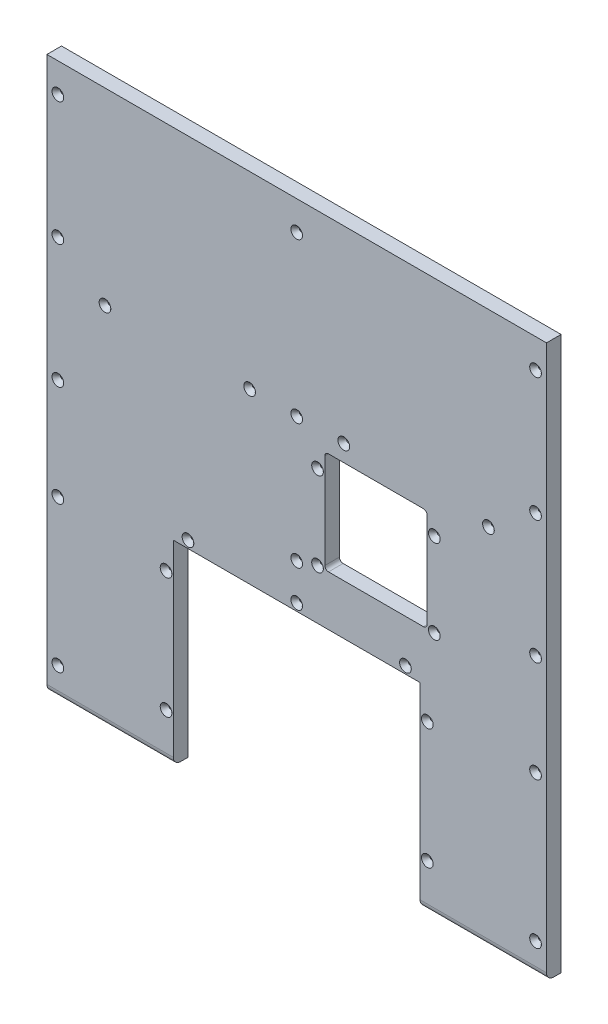
SolidWorks part; units mm, degrees
material "Beech"
ref_plane "Front Plane" through (0, 0, 0) normal (0, 0, 1) x (1, 0, 0)
ref_plane "Top Plane" through (0, 0, 0) normal (0, 1, 0) x (1, 0, 0)
ref_plane "Right Plane" through (0, 0, 0) normal (1, 0, 0) x (0, 0, -1)
sketch "Sketch1" plane through (0, 0, 0) normal (0, 0, 1) x (1, 0, 0)
  line L0 (124.0045, -60.2629) -> (124.0045, 250.6666) construction
  line L1 (16.7045, -230.2629) -> (-93.2955, -230.2629)
  line L2 (16.7045, -60.2629) -> (16.7045, -230.2629)
  line L3 (-93.2955, -230.2629) -> (-93.2955, 250.6666)
  line L16 (341.3045, -230.2629) -> (341.3045, 250.6666)
  line L17 (341.3045, 250.6666) -> (-93.2955, 250.6666)
  line L21 (16.7045, -60.2629) -> (231.3045, -60.2629)
  line L22 (231.3045, -60.2629) -> (231.3045, -230.2629)
  line L23 (231.3045, -230.2629) -> (341.3045, -230.2629)
  dimension "D1" = 434.6
  dimension "D2" = 480.9295
  dimension "D3" = 110
  dimension "D4" = 170
extrude "Boss-Extrude1" add sketch "Sketch1" against normal blind 12.7
fillet "Fillet1" radius 6.35 2 edges at (286.3045, -230.2629, 0) (-38.2955, -230.2629, 0)
hole_wizard "Hole1" positions "Sketch2" profile "Sketch3" legacy end condition through all
sketch "Sketch2" plane through (0, 0, 0) normal (0, 0, 1) x (1, 0, 0)
  line L8 (331.7795, 250.6666) -> (331.7795, -230.2629) construction
  line L9 (341.3045, 250.6666) -> (-93.2955, 250.6666) construction
  line L12 (322.2545, 226.323) -> (322.2545, -204.8629) construction
  line L13 (341.3045, -204.8629) -> (341.3045, 226.323) construction
  line L15 (331.7795, 225.2666) -> (331.7795, 10.2019)
  line L16 (331.7795, 10.2019) -> (331.7795, -204.8629)
  line L17 (133.5295, 86.6832) -> (322.2545, 86.6832) construction
  line L19 (322.2545, 96.2082) -> (133.5295, 96.2082) construction
  line L20 (133.5295, 77.1582) -> (322.2545, 77.1582) construction
  line L21 (133.5295, -47.5629) -> (133.5295, 259.4032) construction
  line L22 (322.2545, 259.4032) -> (322.2545, -217.5629) construction
  line L23 (133.5295, 86.6832) -> (196.4378, 86.6832)
  line L24 (196.4378, 86.6832) -> (259.3461, 86.6832)
  line L25 (259.3461, 86.6832) -> (322.2545, 86.6832)
  line L26 (341.3045, -230.2629) -> (231.3045, -230.2629) construction
  line L27 (237.6545, -60.2629) -> (237.6545, -217.5629) construction
  line L31 (237.6545, -60.2629) -> (237.6545, -112.6962)
  line L32 (237.6545, -112.6962) -> (237.6545, -165.1295)
  line L33 (237.6545, -165.1295) -> (237.6545, -217.5629)
  line L34 (124.0045, 250.6666) -> (124.0045, -47.5629) construction
  line L36 (114.4795, 226.323) -> (114.4795, -49.1129) construction
  line L37 (133.5295, -49.1129) -> (133.5295, 226.323) construction
  line L38 (4.0045, -53.9129) -> (244.0045, -53.9129) construction
  line L40 (4.0045, -47.5629) -> (244.0045, -47.5629) construction
  line L41 (4.0045, -60.2629) -> (244.0045, -60.2629) construction
  line L42 (4.0045, -60.2629) -> (4.0045, -47.5629) construction
  line L43 (244.0045, -47.5629) -> (244.0045, -60.2629) construction
  point P29 (331.7795, -204.8629)
  point P32 (331.7795, 10.2019)
  point P34 (331.7795, 225.2666)
  point P54 (331.7795, 117.7343)
  point P61 (331.7795, -77.8629)
  point P87 (164.9836, 86.6832)
  point P89 (290.8003, 86.6832)
  point P118 (237.6545, -86.4795)
  point P120 (237.6545, -191.3462)
  point P143 (124.0045, 86.6832)
  point P145 (124.0045, 225.2666)
  point P147 (124.0045, -22.1629)
  point P151 (10.3545, -191.3462)
  point P152 (10.3545, -86.4795)
  point P153 (-42.7914, 86.6832)
  point P154 (83.0253, 86.6832)
  point P155 (-83.7705, -77.8629)
  point P156 (-83.7705, 117.7343)
  point P157 (-83.7705, 225.2666)
  point P158 (-83.7705, 10.2019)
  point P159 (-83.7705, -204.8629)
  point P174 (124.0045, -53.9129)
  point P176 (29.4045, -53.9129)
  point P178 (218.6045, -53.9129)
  dimension "D1" = 25.4
  dimension "D2" = 127
  dimension "D3" = 25.4
  dimension "D4" = 25.4
  dimension "D5" = 25.4
  dimension "D6" = 25.4
  dimension "D7" = 25.4
sketch "Sketch3" plane through (218.6045, -53.9129, 0) normal (1, 0, 0) x (0, -1, 0)
  line L0 (0, 0) -> (0, 13.6539)
  line L1 (0, 13.6539) -> (1.5875, 12.7)
  line L2 (1.5875, 12.7) -> (1.5875, 4.0177)
  line L3 (1.5875, 4.0177) -> (5.08, 0)
  line L4 (5.08, 0) -> (0, 0)
  line L5 (0, -14.3089) -> (0, 102.4216) construction
  line L6 (0, 13.6539) -> (-1.5875, 12.7) construction
  line L7 (-1.5875, 4.0177) -> (-5.08, 0) construction
  dimension "Diameter" = 3.175
  dimension "Depth" = 12.7
  dimension "C-Sink Diameter" = 10.16
  dimension "C-Sink Angle" = 82
  dimension "Drill Angle" = 118
hole_wizard "Hole2" positions "Sketch4" profile "Sketch5" legacy
sketch "Sketch4" plane through (124.0045, -215.2871, 0) normal (0, 0, 1) x (1, 0, 0)
  line L1 (0, 465.9538) -> (0, 167.7243) construction
  point P1 (113.65, 128.8076)
  point P3 (113.65, 23.941)
  point P5 (-94.6, 161.3743)
  point P7 (94.6, 161.3743)
  point P9 (0, 161.3743)
  point P11 (0, 193.1243)
  point P13 (0, 440.5538)
  point P15 (0, 301.9704)
  point P17 (40.9792, 301.9704)
  point P19 (166.7958, 301.9704)
  point P21 (207.775, 440.5538)
  point P23 (207.775, 333.0214)
  point P25 (207.775, 225.489)
  point P27 (207.775, 137.4243)
  point P29 (207.775, 10.4243)
  point P33 (-207.775, 10.4243)
  point P34 (-207.775, 137.4243)
  point P35 (-207.775, 225.489)
  point P36 (-207.775, 333.0214)
  point P37 (-207.775, 440.5538)
  point P38 (-166.7958, 301.9704)
  point P39 (-40.9792, 301.9704)
  point P40 (-113.65, 23.941)
  point P41 (-113.65, 128.8076)
sketch "Sketch5" plane through (237.6545, -86.4795, 0) normal (1, 0, 0) x (0, -1, 0)
  line L0 (0, 0) -> (0, 32.7039)
  line L1 (0, 32.7039) -> (1.5875, 31.75)
  line L2 (1.5875, 31.75) -> (1.5875, 4.0177)
  line L3 (1.5875, 4.0177) -> (5.08, 0)
  line L4 (5.08, 0) -> (0, 0)
  line L5 (0, -14.3089) -> (0, 102.4216) construction
  line L6 (0, 32.7039) -> (-1.5875, 31.75) construction
  line L7 (-1.5875, 4.0177) -> (-5.08, 0) construction
  dimension "Diameter" = 3.175
  dimension "Depth" = 31.75
  dimension "C-Sink Diameter" = 10.16
  dimension "C-Sink Angle" = 82
  dimension "Drill Angle" = 118
sketch "Sketch6" plane through (0, 0, 0) normal (0, 0, 1) x (1, 0, 0)
  line L0 (215.1525, 5.5432) -> (170.7025, 49.9932) construction
  line L2 (237.3775, 72.2182) -> (148.4775, 72.2182)
  line L3 (237.3775, 72.2182) -> (237.3775, -16.6818)
  line L4 (237.3775, -16.6818) -> (148.4775, -16.6818)
  line L5 (148.4775, 72.2182) -> (148.4775, -16.6818)
  line L6 (237.3775, 72.2182) -> (148.4775, -16.6818) construction
  line L7 (237.3775, -16.6818) -> (148.4775, 72.2182) construction
  point P4 (192.9275, 27.7682)
  point P9 (192.9275, 27.7682)
  dimension "D1" = 88.9
extrude "Cut-Extrude1" cut sketch "Sketch6" against normal up to next
fillet "Fillet2" radius 3.175 4 edges at (148.4775, 72.2182, -6.35) (148.4775, -16.6818, -6.35) (237.3775, -16.6818, -6.35) (237.3775, 72.2182, -6.35)
hole_wizard "Hole3" positions "Sketch7" profile "Sketch8" legacy
sketch "Sketch7" plane through (124.0045, -215.2871, 0) normal (0, 0, 1) x (1, 0, 0)
  line L1 (0, 465.9538) -> (0, 167.7243) construction
  line L2 (126.073, 235.1179) -> (113.373, 235.1179) construction
  line L6 (119.723, 284.3304) -> (119.723, 185.9054) construction
  line L10 (68.923, 285.9179) -> (68.923, 200.1929) construction
  point P1 (113.65, 128.8076)
  point P3 (113.65, 23.941)
  point P5 (-94.6, 161.3743)
  point P7 (94.6, 161.3743)
  point P9 (0, 161.3743)
  point P11 (0, 193.1243)
  point P13 (0, 440.5538)
  point P15 (0, 301.9704)
  point P17 (40.9792, 301.9704)
  point P19 (166.7958, 301.9704)
  point P21 (207.775, 440.5538)
  point P23 (207.775, 333.0214)
  point P25 (207.775, 225.489)
  point P27 (207.775, 137.4243)
  point P29 (207.775, 10.4243)
  point P33 (-207.775, 10.4243)
  point P34 (-207.775, 137.4243)
  point P35 (-207.775, 225.489)
  point P36 (-207.775, 333.0214)
  point P37 (-207.775, 440.5538)
  point P38 (-166.7958, 301.9704)
  point P39 (-40.9792, 301.9704)
  point P40 (-113.65, 23.941)
  point P41 (-113.65, 128.8076)
  point P65 (119.723, 198.6054)
  point P68 (119.723, 271.6304)
  point P78 (18.123, 198.6054)
  point P79 (18.123, 271.6304)
sketch "Sketch8" plane through (237.6545, -86.4795, 0) normal (1, 0, 0) x (0, -1, 0)
  line L0 (0, 0) -> (0, 32.7039)
  line L1 (0, 32.7039) -> (1.5875, 31.75)
  line L2 (1.5875, 31.75) -> (1.5875, 4.0177)
  line L3 (1.5875, 4.0177) -> (5.08, 0)
  line L4 (5.08, 0) -> (0, 0)
  line L5 (0, -14.3089) -> (0, 102.4216) construction
  line L6 (0, 32.7039) -> (-1.5875, 31.75) construction
  line L7 (-1.5875, 4.0177) -> (-5.08, 0) construction
  dimension "Diameter" = 3.175
  dimension "Depth" = 31.75
  dimension "C-Sink Diameter" = 10.16
  dimension "C-Sink Angle" = 82
  dimension "Drill Angle" = 118
